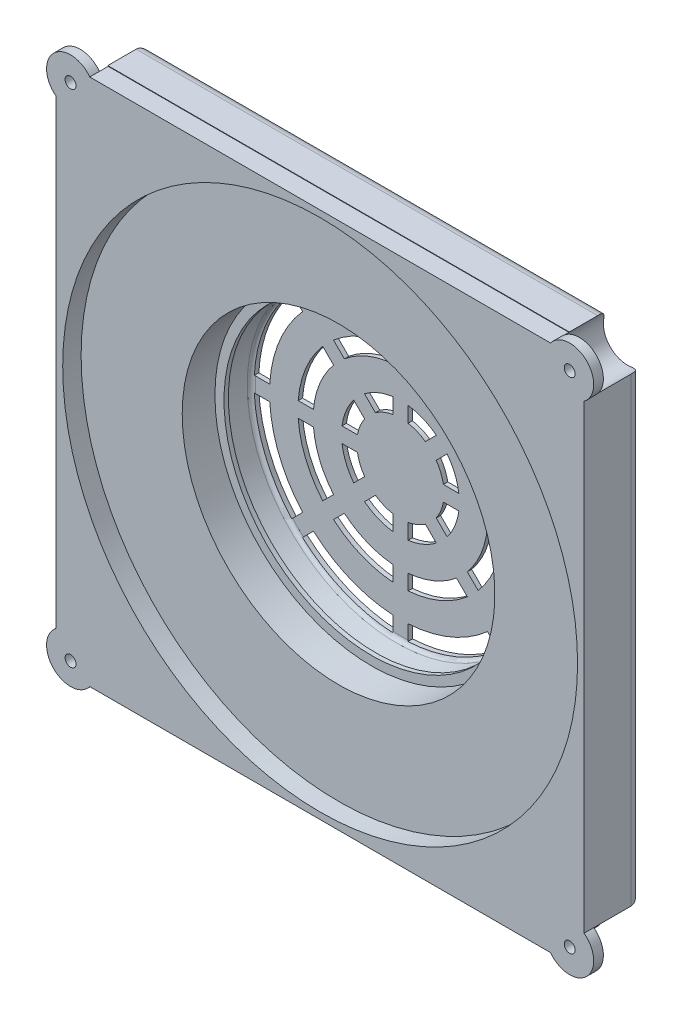
SolidWorks part; units mm, degrees
ref_plane "Front Plane" through (0, 0, 0) normal (0, 0, 1) x (1, 0, 0)
ref_plane "Top Plane" through (0, 0, 0) normal (0, 1, 0) x (1, 0, 0)
ref_plane "Right Plane" through (0, 0, 0) normal (1, 0, 0) x (0, 0, -1)
sketch "Sketch1" plane through (0, 0, 0) normal (0, 1, 0) x (1, 0, 0)
  line L0 (0, 66.7962) -> (0, -77.6353) construction
  line L1 (0, 21.5428) -> (68.2334, 21.5428)
  line L2 (70.2181, 19.7897) -> (71.6628, 8.1763)
  line L3 (71.6628, 8.1763) -> (118, 8.1763)
  line L4 (120, 6.1763) -> (120, 2.7379)
  line L5 (0, 19.5428) -> (66.4668, 19.5428)
  line L6 (68.4515, 17.7897) -> (69.8962, 6.1763)
  line L7 (69.8962, 6.1763) -> (118, 6.1763)
  line L8 (118, 6.1763) -> (118, 2.7379)
  line L9 (118, 2.7379) -> (120, 2.7379)
  line L10 (0, 19.5428) -> (0, 21.5428)
  line L11 (71.6628, 8.1763) -> (120, 8.1763) construction
  line L12 (120, 8.1763) -> (120, 2.7379) construction
  line L13 (0, 19.5428) -> (68.2334, 19.5428) construction
  line L14 (68.2334, 19.5428) -> (69.8962, 6.1763) construction
  line L15 (0, 21.5428) -> (70, 21.5428) construction
  line L16 (70, 21.5428) -> (71.6628, 8.1763) construction
  arc A0 (118, 8.1763) -> (120, 6.1763) centre (118, 6.1763) cw
  arc A1 (66.4668, 19.5428) -> (68.4515, 17.7897) centre (66.4668, 17.5428) cw
  arc A2 (68.2334, 21.5428) -> (70.2181, 19.7897) centre (68.2334, 19.5428) cw
  point P16 (120, 8.1763)
  point P23 (70, 21.5428)
  dimension "D5" = 2
  dimension "D2" = 70
  dimension "D3" = 48.3372
  dimension "D4" = 120
  dimension "D1" = 2
revolve "Revolve9" add sketch "Sketch1" angle 360 about L0
sketch "Sketch2" plane through (0, 0, -2.7379) normal (0, 0, 1) x (1, 0, 0)
  line L0 (-121, -105.5984) -> (-121, 105.5984)
  line L1 (-103.7868, -125) -> (103.7868, -125)
  line L2 (-125, -103.7868) -> (-125, 103.7868)
  line L3 (-103.7868, 125) -> (103.7868, 125)
  line L4 (125, -103.7868) -> (125, 103.7868)
  line L5 (0, 0) -> (103.7868, 103.7868) construction
  line L6 (-103.7868, 103.7868) -> (103.7868, -103.7868) construction
  line L7 (-105.5984, 121) -> (105.5984, 121)
  line L8 (121, -105.5984) -> (121, 105.5984)
  line L9 (-105.5984, -121) -> (105.5984, -121)
  arc A1 (125, 103.7868) -> (103.7868, 125) centre (114.3934, 114.3934) ccw
  arc A2 (103.7868, -125) -> (125, -103.7868) centre (114.3934, -114.3934) ccw
  arc A3 (-125, -103.7868) -> (-103.7868, -125) centre (-114.3934, -114.3934) ccw
  arc A4 (-103.7868, 125) -> (-125, 103.7868) centre (-114.3934, 114.3934) ccw
  arc A5 (-105.5984, 121) -> (-121, 105.5984) centre (-114.3934, 114.3934) ccw
  arc A6 (121, 105.5984) -> (105.5984, 121) centre (114.3934, 114.3934) ccw
  arc A7 (105.5984, -121) -> (121, -105.5984) centre (114.3934, -114.3934) ccw
  arc A8 (-121, -105.5984) -> (-105.5984, -121) centre (-114.3934, -114.3934) ccw
  circle A9 centre (0, 0) radius 118
  point P0 (0, 0)
  circle M3 centre (0, 0) radius 120
  circle M4 centre (0, 0) radius 118
  dimension "D4" = 30
  dimension "D5" = 30
  dimension "D6" = 30
  dimension "D1" = 4
  dimension "D2" = 250
extrude "Boss-Extrude8" add sketch "Sketch2" along normal blind 20 contours L0 A8 L9 A7 L8 A6 L7 A5 M3 | M4 | L0 A5 L7 A6 L8 A7 L9 A8 region at (-120.6453, 0, -2.7379) region at (0, 0, -2.7379)
sketch "Sketch4" plane through (0, 0, -2.7379) normal (0, 0, -1) x (-1, 0, 0)
  line L0 (0, 169.0104) -> (0, -169.8195) construction
  line L1 (0, -169.8195) -> (-226.6467, -0.4045) construction
  line L2 (-226.6467, -0.4045) -> (252.7516, -0.4045) construction
  circle A0 centre (-114.3934, 114.3934) radius 11
  circle A1 centre (-114.3934, -115.2024) radius 11
  circle A2 centre (114.3934, 114.3934) radius 11
  circle A3 centre (114.3934, -115.2024) radius 11
extrude "Cut-Extrude3" cut sketch "Sketch4" against normal blind 15
sketch "Sketch5" plane through (0, 0, 12.2621) normal (0, 0, -1) x (-1, 0, 0)
  circle A0 centre (-114.3934, 114.3934) radius 2.5
  circle A1 centre (114.3934, 114.3934) radius 2.5
  circle A2 centre (-114.3934, -114.3934) radius 2.5
  circle A3 centre (114.3934, -115.2024) radius 2.5
  dimension "D1" = 5
  dimension "D2" = 5
  dimension "D3" = 5
  dimension "D4" = 5
extrude "Cut-Extrude4" cut sketch "Sketch5" against normal blind 75
sketch "Sketch6" plane through (0, 0, -21.5428) normal (0, 0, -1) x (-1, 0, 0)
  line L0 (0, 132.0266) -> (0, -136.9229) construction
  line L1 (0, -136.9229) -> (-151.7868, -2.4482) construction
  line L2 (-139.546, 0) -> (180.1157, 0) construction
  line L3 (0, 0) -> (-68.2334, 0) construction
  line L4 (0, 0) -> (-114.3934, 114.3934) construction
  line L5 (-30.6507, 25.7009) -> (-35.6166, 30.6669)
  line L6 (-66.9085, 3.5) -> (-59.8978, 3.5)
  line L7 (-44.829, 39.8793) -> (-49.7863, 44.8366)
  line L8 (-139.546, 3.5) -> (180.1157, 3.5) construction
  line L9 (-16.3988, 11.449) -> (-21.4057, 16.4559)
  line L10 (-26.7722, 3.5) -> (-19.6914, 3.5)
  line L11 (-46.8695, 3.5) -> (-39.8466, 3.5)
  line L12 (-44.8366, 49.7863) -> (-39.8793, 44.829)
  line L13 (-3.5, 59.8978) -> (-3.5, 66.9085)
  line L14 (-3.5, 39.8466) -> (-3.5, 46.8695)
  line L15 (-30.6669, 35.6166) -> (-25.7009, 30.6507)
  line L16 (-16.4559, 21.4057) -> (-11.449, 16.3988)
  line L17 (-3.5, 19.6914) -> (-3.5, 26.7722)
  line L18 (3.5, 66.9085) -> (3.5, 59.8978)
  line L19 (39.8793, 44.829) -> (44.8366, 49.7863)
  line L20 (25.7009, 30.6507) -> (30.6669, 35.6166)
  line L21 (3.5, 46.8695) -> (3.5, 39.8466)
  line L22 (3.5, 26.7722) -> (3.5, 19.6914)
  line L23 (11.449, 16.3988) -> (16.4559, 21.4057)
  line L24 (49.7863, 44.8366) -> (44.829, 39.8793)
  line L25 (59.8978, 3.5) -> (66.9085, 3.5)
  line L26 (39.8466, 3.5) -> (46.8695, 3.5)
  line L27 (35.6166, 30.6669) -> (30.6507, 25.7009)
  line L28 (21.4057, 16.4559) -> (16.3988, 11.449)
  line L29 (19.6914, 3.5) -> (26.7722, 3.5)
  line L30 (66.9085, -3.5) -> (59.8978, -3.5)
  line L31 (44.829, -39.8793) -> (49.7863, -44.8366)
  line L32 (30.6507, -25.7009) -> (35.6166, -30.6669)
  line L33 (46.8695, -3.5) -> (39.8466, -3.5)
  line L34 (26.7722, -3.5) -> (19.6914, -3.5)
  line L35 (16.3988, -11.449) -> (21.4057, -16.4559)
  line L36 (44.8366, -49.7863) -> (39.8793, -44.829)
  line L37 (3.5, -59.8978) -> (3.5, -66.9085)
  line L38 (3.5, -39.8466) -> (3.5, -46.8695)
  line L39 (30.6669, -35.6166) -> (25.7009, -30.6507)
  line L40 (16.4559, -21.4057) -> (11.449, -16.3988)
  line L41 (3.5, -19.6914) -> (3.5, -26.7722)
  line L42 (-3.5, -66.9085) -> (-3.5, -59.8978)
  line L43 (-39.8793, -44.829) -> (-44.8366, -49.7863)
  line L44 (-25.7009, -30.6507) -> (-30.6669, -35.6166)
  line L45 (-3.5, -46.8695) -> (-3.5, -39.8466)
  line L46 (-3.5, -26.7722) -> (-3.5, -19.6914)
  line L47 (-11.449, -16.3988) -> (-16.4559, -21.4057)
  line L48 (-49.7863, -44.8366) -> (-44.829, -39.8793)
  line L49 (-59.8978, -3.5) -> (-66.9085, -3.5)
  line L50 (-39.8466, -3.5) -> (-46.8695, -3.5)
  line L51 (-35.6166, -30.6669) -> (-30.6507, -25.7009)
  line L52 (-21.4057, -16.4559) -> (-16.3988, -11.449)
  line L53 (-19.6914, -3.5) -> (-26.7722, -3.5)
  circle A0 centre (0, 0) radius 68.2334 construction
  arc A1 (-30.6507, 25.7009) -> (-39.8466, 3.5) centre (0, 0) ccw
  arc A2 (-44.829, 39.8793) -> (-59.8978, 3.5) centre (0, 0) ccw
  arc A3 (-21.4057, 16.4559) -> (-26.7722, 3.5) centre (0, 0) ccw
  arc A4 (-16.3988, 11.449) -> (-19.6914, 3.5) centre (0, 0) ccw
  arc A5 (-35.6166, 30.6669) -> (-46.8695, 3.5) centre (0, 0) ccw
  arc A6 (-49.7863, 44.8366) -> (-66.9085, 3.5) centre (0, 0) ccw
  arc A7 (0, 67) -> (-67, 0) centre (0, 0) ccw construction
  arc A8 (0, 60) -> (-60, 0) centre (0, 0) ccw construction
  arc A9 (0, 47) -> (-47, 0) centre (0, 0) ccw construction
  arc A10 (0, 40) -> (-40, 0) centre (0, 0) ccw construction
  arc A11 (0, 27) -> (-26.9378, -1.8311) centre (0, 0) ccw construction
  arc A12 (0, 20) -> (-19.954, -1.3564) centre (0, 0) ccw construction
  arc A13 (-27, 0) -> (-26.9378, -1.8311) centre (0, 0) ccw
  arc A14 (-20, 0) -> (-19.954, -1.3564) centre (0, 0) ccw
  arc A15 (-3.5, 59.8978) -> (-39.8793, 44.829) centre (0, 0) ccw
  arc A16 (-3.5, 66.9085) -> (-44.8366, 49.7863) centre (0, 0) ccw
  arc A17 (-3.5, 46.8695) -> (-30.6669, 35.6166) centre (0, 0) ccw
  arc A18 (-3.5, 39.8466) -> (-25.7009, 30.6507) centre (0, 0) ccw
  arc A19 (-3.5, 26.7722) -> (-16.4559, 21.4057) centre (0, 0) ccw
  arc A20 (-3.5, 19.6914) -> (-11.449, 16.3988) centre (0, 0) ccw
  arc A21 (39.8793, 44.829) -> (3.5, 59.8978) centre (0, 0) ccw
  arc A22 (44.8366, 49.7863) -> (3.5, 66.9085) centre (0, 0) ccw
  arc A23 (30.6669, 35.6166) -> (3.5, 46.8695) centre (0, 0) ccw
  arc A24 (25.7009, 30.6507) -> (3.5, 39.8466) centre (0, 0) ccw
  arc A25 (16.4559, 21.4057) -> (3.5, 26.7722) centre (0, 0) ccw
  arc A26 (11.449, 16.3988) -> (3.5, 19.6914) centre (0, 0) ccw
  arc A27 (59.8978, 3.5) -> (44.829, 39.8793) centre (0, 0) ccw
  arc A28 (66.9085, 3.5) -> (49.7863, 44.8366) centre (0, 0) ccw
  arc A29 (46.8695, 3.5) -> (35.6166, 30.6669) centre (0, 0) ccw
  arc A30 (39.8466, 3.5) -> (30.6507, 25.7009) centre (0, 0) ccw
  arc A31 (26.7722, 3.5) -> (21.4057, 16.4559) centre (0, 0) ccw
  arc A32 (19.6914, 3.5) -> (16.3988, 11.449) centre (0, 0) ccw
  arc A33 (44.829, -39.8793) -> (59.8978, -3.5) centre (0, 0) ccw
  arc A34 (49.7863, -44.8366) -> (66.9085, -3.5) centre (0, 0) ccw
  arc A35 (35.6166, -30.6669) -> (46.8695, -3.5) centre (0, 0) ccw
  arc A36 (30.6507, -25.7009) -> (39.8466, -3.5) centre (0, 0) ccw
  arc A37 (21.4057, -16.4559) -> (26.7722, -3.5) centre (0, 0) ccw
  arc A38 (16.3988, -11.449) -> (19.6914, -3.5) centre (0, 0) ccw
  arc A39 (3.5, -59.8978) -> (39.8793, -44.829) centre (0, 0) ccw
  arc A40 (3.5, -66.9085) -> (44.8366, -49.7863) centre (0, 0) ccw
  arc A41 (3.5, -46.8695) -> (30.6669, -35.6166) centre (0, 0) ccw
  arc A42 (3.5, -39.8466) -> (25.7009, -30.6507) centre (0, 0) ccw
  arc A43 (3.5, -26.7722) -> (16.4559, -21.4057) centre (0, 0) ccw
  arc A44 (3.5, -19.6914) -> (11.449, -16.3988) centre (0, 0) ccw
  arc A45 (-39.8793, -44.829) -> (-3.5, -59.8978) centre (0, 0) ccw
  arc A46 (-44.8366, -49.7863) -> (-3.5, -66.9085) centre (0, 0) ccw
  arc A47 (-30.6669, -35.6166) -> (-3.5, -46.8695) centre (0, 0) ccw
  arc A48 (-25.7009, -30.6507) -> (-3.5, -39.8466) centre (0, 0) ccw
  arc A49 (-16.4559, -21.4057) -> (-3.5, -26.7722) centre (0, 0) ccw
  arc A50 (-11.449, -16.3988) -> (-3.5, -19.6914) centre (0, 0) ccw
  arc A51 (-59.8978, -3.5) -> (-44.829, -39.8793) centre (0, 0) ccw
  arc A52 (-66.9085, -3.5) -> (-49.7863, -44.8366) centre (0, 0) ccw
  arc A53 (-46.8695, -3.5) -> (-35.6166, -30.6669) centre (0, 0) ccw
  arc A54 (-39.8466, -3.5) -> (-30.6507, -25.7009) centre (0, 0) ccw
  arc A55 (-26.7722, -3.5) -> (-21.4057, -16.4559) centre (0, 0) ccw
  arc A56 (-19.6914, -3.5) -> (-16.3988, -11.449) centre (0, 0) ccw
  point P130 (0, 0)
  dimension "D2" = 20
  dimension "D3" = 40
  dimension "D4" = 60
  dimension "D1" = 68.2334
  dimension "D5" = 7
  dimension "D6" = 8
  dimension "D7" = 3.5
extrude "Cut-Extrude5" cut sketch "Sketch6" along normal blind 59 and the other way blind 200 contours L19 A22 L18 A21 | L25 A28 L24 A27 | A24 L20 A23 L21 | A30 L26 A29 L27 | A18 L14 A17 L15 | L13 A16 L12 A15 | L5 A5 L11 A1 | A54 L50 A53 L51 | L49 A52 L48 A51 | A56 L53 A55 L52 | A4 L9 A3 L10 | A32 L29 A31 L28 | L7 A6 L6 A2 | A50 L47 A49 L46 | A44 L41 A43 L40 | A38 L35 A37 L34 | A36 L32 A35 L33 | A42 L38 A41 L39 | A48 L44 A47 L45 | L43 A46 L42 A45 | L37 A40 L36 A39 | L31 A34 L30 A33 | A20 L17 A19 L16 | A26 L23 A25 L22 region at (39.6457, 16.4218, -21.5428) region at (57.626, 23.8695, -21.5428) region at (21.7515, 9.0098, -21.5428) region at (23.8695, 57.626, -21.5428) region at (16.4218, 39.6457, -21.5428) region at (9.0098, 21.7515, -21.5428) region at (-23.8695, 57.626, -21.5428) region at (-16.4218, 39.6457, -21.5428) region at (-9.0098, 21.7515, -21.5428) region at (-57.626, 23.8695, -21.5428) region at (-39.6457, 16.4218, -21.5428) region at (-21.7515, 9.0098, -21.5428) region at (-57.626, -23.8695, -21.5428) region at (-39.6457, -16.4218, -21.5428) region at (-21.7515, -9.0098, -21.5428) region at (-23.8695, -57.626, -21.5428) region at (-16.4218, -39.6457, -21.5428) region at (-9.0098, -21.7515, -21.5428) region at (23.8695, -57.626, -21.5428) region at (16.4218, -39.6457, -21.5428) region at (9.0098, -21.7515, -21.5428) region at (57.626, -23.8695, -21.5428) region at (39.6457, -16.4218, -21.5428) region at (21.7515, -9.0098, -21.5428)
sketch "Sketch7" plane through (0, 0, -6.1763) normal (0, 0, 1) x (1, 0, 0)
  line L1 (121, -121.2293) -> (-121, -121.2293)
  line L2 (121, -121.2293) -> (121, 121.2293)
  line L3 (121, 121.2293) -> (-121, 121.2293)
  line L4 (-121, -121.2293) -> (-121, 121.2293)
  line L5 (121, -121.2293) -> (-121, 121.2293) construction
  line L6 (121, 121.2293) -> (-121, -121.2293) construction
  point P0 (0, 0)
extrude "Boss-Extrude9" add sketch "Sketch7" against normal blind 2
sketch "Sketch8" plane through (0, 0, -6.1763) normal (0, 0, 1) x (1, 0, 0)
  circle A0 centre (0, 0) radius 67.5
  dimension "D1" = 135
extrude "Cut-Extrude7" cut sketch "Sketch8" against normal blind 2
sketch "Sketch9" plane through (0, 0, -8.1763) normal (0, 0, -1) x (-1, 0, 0)
  line L1 (-105.7754, -121.2293) -> (105.7754, -121.2293)
  line L2 (-121, -105.5984) -> (-121, 105.5984)
  line L3 (-105.7754, 121.2293) -> (105.7754, 121.2293)
  line L4 (121, -105.5984) -> (121, 105.5984)
  line L5 (-106.515, -106.7168) -> (106.515, 106.7168) construction
  line L6 (-106.515, 106.7168) -> (106.515, -106.7168) construction
  circle A0 centre (0, 0) radius 71.6628
  arc A1 (-121, 105.5984) -> (-105.7754, 121.2293) centre (-114.3934, 114.3934) ccw
  arc A2 (105.7754, 121.2293) -> (121, 105.5984) centre (114.3934, 114.3934) ccw
  arc A3 (-105.7754, -121.2293) -> (-121, -105.5984) centre (-114.3934, -114.3934) ccw
  arc A4 (121, -105.5984) -> (105.7754, -121.2293) centre (114.3934, -114.3934) ccw
  point P0 (0, 0)
extrude "Boss-Extrude12" add sketch "Sketch9" against normal blind 17 and the other way blind 1
sketch "Sketch10" plane through (0, 0, -9.1763) normal (0, 0, -1) x (-1, 0, 0)
  circle A0 centre (-114.3934, 114.3934) radius 11
  circle A1 centre (114.3934, 114.3934) radius 11
  circle A2 centre (-114.3934, -114.3934) radius 11
  circle A3 centre (114.3934, -114.3934) radius 11
  dimension "D1" = 22
  dimension "D2" = 22
extrude "Cut-Extrude11" cut sketch "Sketch10" against normal blind 22
fillet "Fillet5" radius 5 4 edges at (-121, 0, -9.1763) (0, -121.2293, -9.1763) (121, 0, -9.1763) (0, 121.2293, -9.1763)
